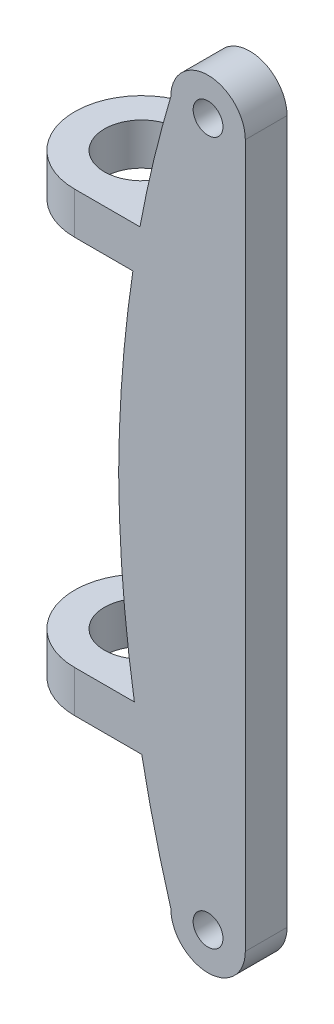
SolidWorks part; units mm, degrees
ref_plane "Alzado" through (0, 0, 0) normal (0, 0, 1) x (1, 0, 0)
ref_plane "Planta" through (0, 0, 0) normal (0, 1, 0) x (1, 0, 0)
ref_plane "Vista lateral" through (0, 0, 0) normal (1, 0, 0) x (0, 0, -1)
sketch "Croquis2" plane through (0, 0, 0) normal (0, 0, 1) x (1, 0, 0)
  line L0 (-3.4288, 24.4572) -> (-2.0113, 21.3193)
  line L1 (-2.0113, -20.6962) -> (-3.4288, -23.8341)
  circle A0 centre (2.3466, 23.8978) radius 1
  circle A1 centre (2.3466, -23.2748) radius 1
  arc A2 (-2.4295, 27.1032) -> (-3.4288, 24.4572) centre (-1.6061, 25.2805) ccw
  arc A3 (-2.0113, 21.3193) -> (0.7191, 20.3605) centre (-0.1886, 22.1426) ccw
  arc A4 (0.7191, -19.7374) -> (-2.0113, -20.6962) centre (-0.1886, -21.5196) ccw
  arc A5 (-3.4288, -23.8341) -> (-2.4295, -26.4801) centre (-1.6061, -24.6575) ccw
sketch "Croquis3" plane through (0, 0, 0) normal (0, 0, 1) x (1, 0, 0)
  line L0 (2.3466, -23.2748) -> (2.3466, 23.8978) construction
  line L2 (2.3466, 0.3115) -> (14.3982, 0.3115) construction
  line L3 (2.3466, 0.3115) -> (-3.6534, 0.3115) construction
  line L4 (4.8466, 23.8978) -> (4.8466, -23.2748)
  circle A0 centre (2.3466, 23.8978) radius 1
  arc A3 (4.8466, 23.8978) -> (-0.1534, 23.8978) centre (2.3466, 23.8978) ccw
  arc A5 (-3.6534, 0.3115) -> (-0.1534, 23.8978) centre (81.1613, -0.2214) cw
  arc A6 (-3.6534, 0.3115) -> (-0.1534, -23.2748) centre (81.1613, 0.8445) ccw
  arc A7 (4.8466, -23.2748) -> (-0.1534, -23.2748) centre (2.3466, -23.2748) cw
  circle A8 centre (2.3466, -23.2748) radius 1
  point P16 (4.8466, 0.3115)
extrude "Saliente-Extruir1" add sketch "Croquis3" along normal blind 2.8
sketch "Croquis4" plane through (0, 0, 0) normal (0, 1, 0) x (1, 0, 0)
  line L2 (4.8466, 0) -> (-4.2673, 5.5445)
  line L3 (-6.6061, -2.8) -> (-3.6534, -2.8)
  line L4 (4.8466, 0) -> (4.8466, -2.8)
  line L5 (4.8466, -2.8) -> (-3.6534, -2.8)
  circle A0 centre (-6.6061, 1.7) radius 2.5
  arc A1 (-4.2673, 5.5445) -> (-6.6061, -2.8) centre (-6.6061, 1.7) ccw
  dimension "D1" = 5
  dimension "D2" = 2
extrude "Saliente-Extruir2" add sketch "Croquis4" along normal blind 2.8 from offset 12.5
extrude "Saliente-Extruir3" add sketch "Croquis4<2>" against normal blind 2.8 from offset 12.5 offset against normal yes
sketch "Croquis4<2>" plane through (0, 0, 0) normal (0, 1, 0) x (1, 0, 0) same geometry as "Croquis4"
